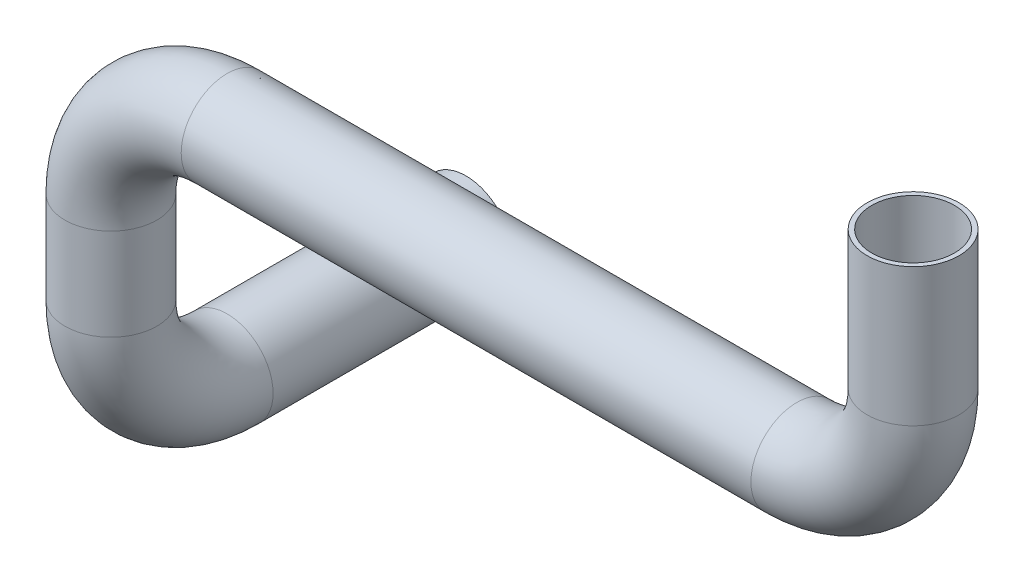
SolidWorks part; units mm, degrees
ref_plane "Front Plane" through (0, 0, 0) normal (0, 0, 1) x (1, 0, 0)
ref_plane "Top Plane" through (0, 0, 0) normal (0, 1, 0) x (1, 0, 0)
ref_plane "Right Plane" through (0, 0, 0) normal (1, 0, 0) x (0, 0, -1)
sketch3d "3DSketch2"
  line L0 (0, 0, 0) -> (0, -15, 0)
  line L1 (-12.65, -27.65, 0) -> (-74.65, -27.65, 0)
  line L2 (-87.3, -40.3, 0) -> (-87.3, -50.3, 0)
  line L3 (-87.3, -62.95, -12.65) -> (-87.3, -62.95, -38.65)
  arc A0 (0, -15, 0) -> (-12.65, -27.65, 0) centre (-12.65, -15, 0) ccw
  arc A1 (-74.65, -27.65, 0) -> (-87.3, -40.3, 0) centre (-74.65, -40.3, 0) ccw
  arc A2 (-87.3, -50.3, 0) -> (-87.3, -62.95, -12.65) centre (-87.3, -50.3, -12.65) ccw
  point P8 (0, -27.65, 0)
  point P9 (-12.65, -15, -12.65)
  point P12 (-87.3, -27.65, 0)
  point P13 (-74.65, -40.3, 12.65)
  point P16 (-87.3, -62.95, 0)
  point P17 (-74.65, -50.3, -12.65)
  dimension "D1" = 12.65
  dimension "D2" = 12.65
  dimension "D3" = 12.65
  dimension "D4" = 15
  dimension "D5" = 62
  dimension "D6" = 10
  dimension "D7" = 26
sweep "Sweep-Thin1" add path "3DSketch2" circular profile diameter 10 parameters "D1"=0.5, "D3"=10
